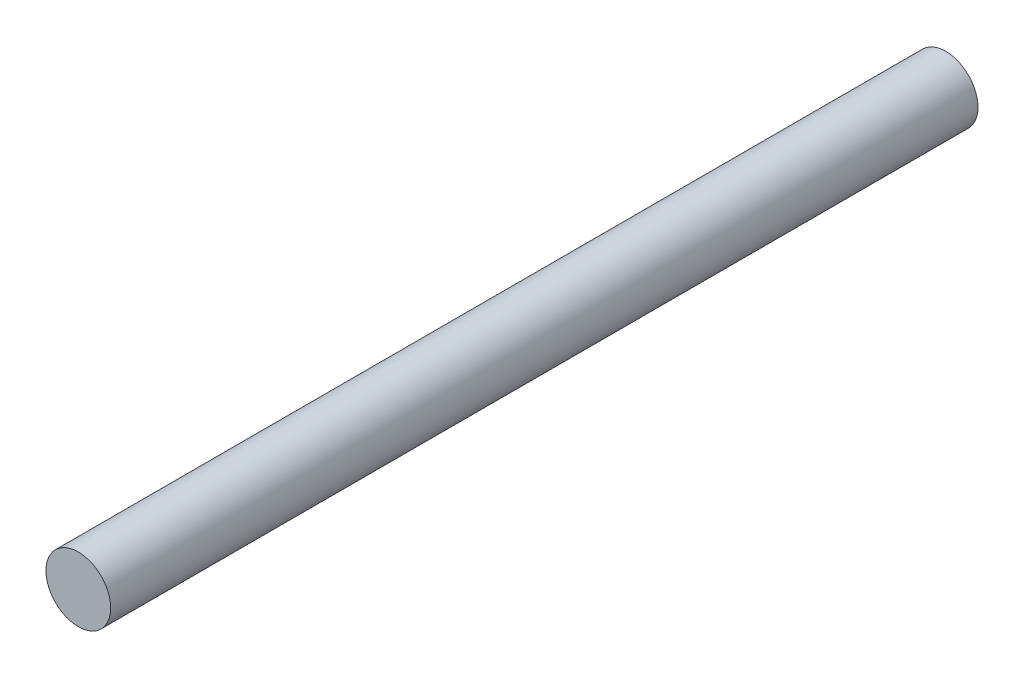
SolidWorks part; units mm, degrees
material "Acciaio in lega fuso"
ref_plane "Piano frontale" through (0, 0, 0) normal (0, 0, 1) x (1, 0, 0)
ref_plane "Piano superiore" through (0, 0, 0) normal (0, 1, 0) x (1, 0, 0)
ref_plane "Piano destro" through (0, 0, 0) normal (1, 0, 0) x (0, 0, -1)
sketch "Schizzo1" plane through (0, 0, 0) normal (0, 0, 1) x (1, 0, 0)
  circle A0 centre (0, 0) radius 2.5
  dimension "D1" = 5
extrude "Estrusione-Estrusione1" add sketch "Schizzo1" along normal blind 33.5 and the other way blind 33.5
chamfer "Smusso1" [suppressed] distance 0.5 angle 45
